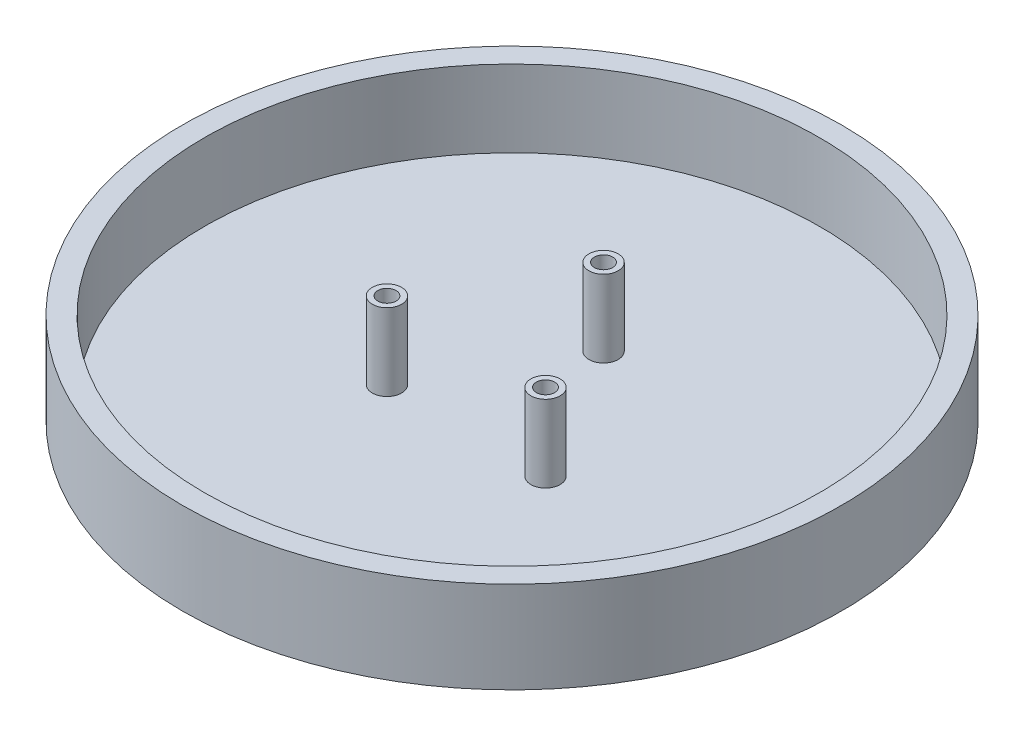
SolidWorks part; units mm, degrees
ref_plane "Front" through (0, 0, 0) normal (0, 0, 1) x (1, 0, 0)
ref_plane "Top" through (0, 0, 0) normal (0, 1, 0) x (1, 0, 0)
ref_plane "Right" through (0, 0, 0) normal (1, 0, 0) x (0, 0, -1)
sketch "Sketch1" plane through (0, 0, 0) normal (0, 1, 0) x (1, 0, 0)
  line L0 (0, 0) -> (0, 12.5) construction
  circle A0 centre (0, 0) radius 42
  circle A1 centre (0, 12.5) radius 1.25
  circle A2 centre (0, 12.5) radius 2
  circle A3 centre (0, 12.5) radius 0.8
  circle A4 centre (10.8253, -6.25) radius 2
  circle A5 centre (10.8253, -6.25) radius 1.25
  circle A6 centre (10.8253, -6.25) radius 0.8
  circle A7 centre (-10.8253, -6.25) radius 2
  circle A8 centre (-10.8253, -6.25) radius 1.25
  circle A9 centre (-10.8253, -6.25) radius 0.8
  circle A10 centre (0, 0) radius 45
  dimension "D1" = 84
  dimension "D3" = 2.5
  dimension "D4" = 4
  dimension "D5" = 1.6
  dimension "D7" = 90
  dimension "D2" = 12.5
  dimension "D6" = 3
extrude "Boss-Extrude1" add sketch "Sketch1" along normal blind 2 contours A0 A7 A4 A2 | A8 A9 | A5 A6 | A1 A3 region at (0, 0, 0) region at (-1.2146, 0, -12.5) region at (9.6107, 0, 6.25) region at (-12.04, 0, 6.25)
extrude "Boss-Extrude2" add sketch "Sketch1<3>" along normal blind 12.5 contours A10 A0 | A4 | A5 | A7 | A8 | A2 | A1 region at (-43.7272, 0, 0)
sketch "Sketch1<3>" plane through (0, 0, 0) normal (0, 1, 0) x (1, 0, 0) same geometry as "Sketch1"
